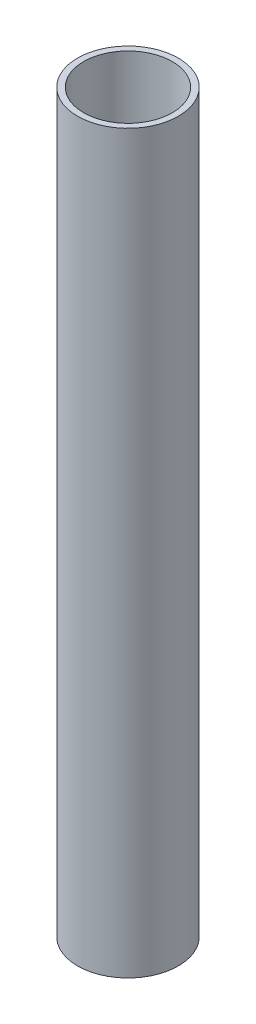
SolidWorks part; units mm, degrees
ref_plane "Front Plane" through (0, 0, 0) normal (0, 0, 1) x (1, 0, 0)
ref_plane "Top Plane" through (0, 0, 0) normal (0, 1, 0) x (1, 0, 0)
ref_plane "Right Plane" through (0, 0, 0) normal (1, 0, 0) x (0, 0, -1)
sketch "Sketch1" plane through (0, 0, 0) normal (0, 1, 0) x (1, 0, 0)
  circle A0 centre (0, 0) radius 1.25
  circle A1 centre (0, 0) radius 1.1
  dimension "D1" = 2.5
  dimension "D2" = 0.15
extrude "Boss-Extrude1" add sketch "Sketch1" along normal blind 18.25
